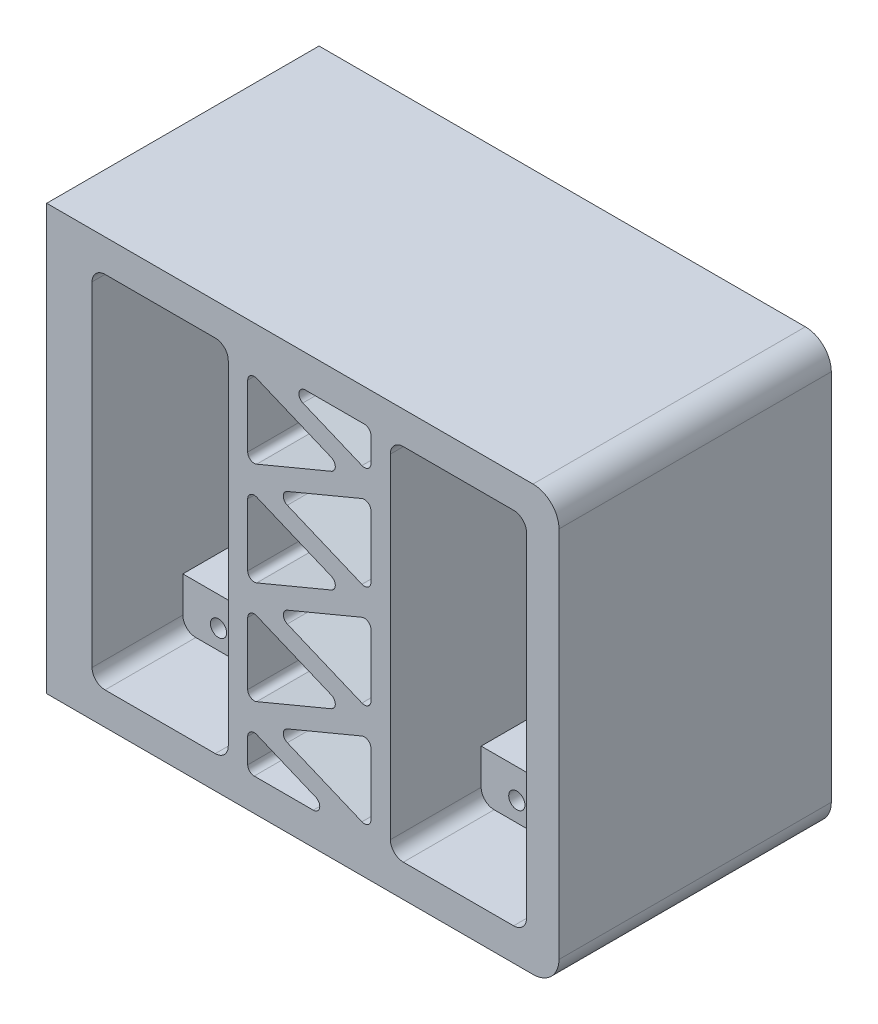
SolidWorks part; units mm, degrees
ref_plane "Front Plane" through (0, 0, 0) normal (0, 0, 1) x (1, 0, 0)
ref_plane "Top Plane" through (0, 0, 0) normal (0, 1, 0) x (1, 0, 0)
ref_plane "Right Plane" through (0, 0, 0) normal (1, 0, 0) x (0, 0, -1)
sketch "Sketch1" plane through (0, 0, 0) normal (0, 0, 1) x (1, 0, 0)
  line L0 (5, 60.5) -> (26, 60.5)
  line L1 (0, 0) -> (77, 0)
  line L2 (0, 0) -> (0, 65.5)
  line L3 (0, 65.5) -> (77, 65.5)
  line L4 (77, 0) -> (77, 65.5)
  line L5 (51, 60.5) -> (72, 60.5)
  line L6 (51, 60.5) -> (51, 5)
  line L7 (51, 5) -> (72, 5)
  line L8 (72, 60.5) -> (72, 5)
  line L9 (5, 60.5) -> (5, 5)
  line L10 (5, 5) -> (26, 5)
  line L12 (26, 60.5) -> (26, 5)
  line L13 (5, 53) -> (26, 53)
  line L14 (51, 53) -> (72, 53)
  line L15 (5, 12.5) -> (26, 12.5)
  line L16 (51, 12.5) -> (72, 12.5)
  line L17 (10.5, 57.5) -> (20.5, 57.5) construction
  line L18 (10.5, 8) -> (20.5, 8) construction
  line L19 (15.5, 57.5) -> (15.5, 8) construction
  line L20 (5, 32.75) -> (26, 32.75) construction
  line L21 (51, 32.75) -> (72, 32.75) construction
  line L22 (61.5, 57.5) -> (61.5, 8) construction
  line L23 (56.5, 57.5) -> (66.5, 57.5) construction
  line L24 (56.5, 8) -> (66.5, 8) construction
  circle A0 centre (10.5, 57.5) radius 1.25
  circle A1 centre (20.5, 57.5) radius 1.25
  circle A2 centre (10.5, 8) radius 1.25
  circle A3 centre (20.5, 8) radius 1.25
  circle A4 centre (56.5, 57.5) radius 1.25
  circle A5 centre (66.5, 57.5) radius 1.25
  circle A6 centre (66.5, 8) radius 1.25
  circle A7 centre (56.5, 8) radius 1.25
  point P33 (15.5, 32.75)
  point P34 (15.5, 32.75)
  point P41 (61.5, 32.75)
  point P42 (61.5, 32.75)
  point P53 (61.5, 8)
  point P55 (61.5, 57.5)
  dimension "D13" = 2.5
  dimension "D1" = 21
  dimension "D2" = 5
  dimension "D3" = 55.5
  dimension "D4" = 55.5
  dimension "D5" = 21
  dimension "D6" = 5
  dimension "D7" = 5
  dimension "D8" = 25
  dimension "D9" = 5
  dimension "D10" = 7.5
  dimension "D11" = 7.5
  dimension "D12" = 10
  dimension "D15" = 49.5
extrude "Boss-Extrude2" add sketch "Sketch1" against normal blind 28 contours L1 L4 L3 L2 L5 L8 L7 L6 L0 L12 L10 L9 | L9 L13 L12 L0 | L15 L9 L10 L12 | L16 L6 L7 L8 | L6 L14 L8 L5 | A0 | A1 | A4 | A5 | A6 | A7 | A3 | A2 region at (15.5, 56.7001, 0) region at (15.5, 8.7999, 0) region at (38.5, 32.75, 0) region at (61.5, 56.7001, 0) region at (61.5, 8.7999, 0) region at (10.5, 57.5, 0) region at (20.5, 57.5, 0) region at (56.5, 57.5, 0) region at (66.5, 57.5, 0) region at (66.5, 8, 0) region at (56.5, 8, 0)
extrude "Boss-Extrude4" add sketch "Sketch1<4>" along normal blind 14 contours L1 L4 L3 L2 L5 L8 L7 L6 L0 L12 L10 L9 region at (38.5, 32.75, 0)
sketch "Sketch1<4>" plane through (0, 0, 0) normal (0, 0, 1) x (1, 0, 0) same geometry as "Sketch1"
extrude "Cut-Extrude1" cut sketch "Sketch1<5>" against normal blind 12 contours A0 | A2 | A3 | A7 | A6 | A4 | A1 | A5 region at (10.5, 57.5, 0) region at (10.5, 8, 0) region at (20.5, 8, 0) region at (56.5, 57.5, 0) region at (66.5, 8, 0) region at (56.5, 8, 0)
sketch "Sketch1<5>" plane through (0, 0, 0) normal (0, 0, 1) x (1, 0, 0) same geometry as "Sketch1"
sketch "Sketch5" plane through (0, 0, 14) normal (0, 0, 1) x (1, 0, 0)
  line L0 (28.4223, 59.1157) -> (44.105, 52.5714)
  line L1 (26, 5) -> (51, 5)
  line L2 (26, 5) -> (26, 60.5)
  line L3 (26, 60.5) -> (51, 60.5)
  line L4 (51, 5) -> (51, 60.5)
  line L5 (26, 60.5) -> (26, 5) construction
  line L6 (51, 60.5) -> (51, 5) construction
  line L7 (5, 60.5) -> (26, 60.5) construction
  line L8 (5, 5) -> (26, 5) construction
  line L9 (29, 60.5) -> (48, 60.5)
  line L10 (48, 5) -> (48, 60.5)
  line L11 (29, 5) -> (48, 5)
  line L12 (29, 5) -> (29, 60.5)
  line L13 (29, 60.5) -> (48, 52.5714)
  line L14 (48, 52.5714) -> (29, 44.6429)
  line L15 (29, 44.6429) -> (48, 36.7143)
  line L16 (48, 36.7143) -> (29, 28.7857)
  line L17 (29, 28.7857) -> (48, 20.8571)
  line L18 (48, 20.8571) -> (29, 12.9286)
  line L19 (29, 12.9286) -> (48, 5)
  line L20 (44.105, 52.5714) -> (25.105, 44.6429)
  line L21 (25.105, 44.6429) -> (44.105, 36.7143)
  line L22 (44.105, 36.7143) -> (25.105, 28.7857)
  line L23 (25.105, 28.7857) -> (44.105, 20.8571)
  line L24 (44.105, 20.8571) -> (25.105, 12.9286)
  line L25 (25.105, 12.9286) -> (47.4223, 3.6157)
  line L26 (29.5777, 61.8843) -> (51.895, 52.5714)
  line L27 (51.895, 52.5714) -> (32.895, 44.6429)
  line L28 (32.895, 44.6429) -> (51.895, 36.7143)
  line L29 (51.895, 36.7143) -> (32.895, 28.7857)
  line L30 (32.895, 28.7857) -> (51.895, 20.8571)
  line L31 (51.895, 20.8571) -> (32.895, 12.9286)
  line L32 (32.895, 12.9286) -> (48.5777, 6.3843)
  dimension "D2" = 1.5
  dimension "D1" = 3
  dimension "D4" = 3
  dimension "D3" = 1.5
extrude "Cut-Extrude2" cut sketch "Sketch5" against normal through all contours L20 L0 L12 | L9 L26 L10 | L27 L28 L10 | L22 L21 L12 | L29 L30 L10 | L24 L23 L12 | L31 L32 L10 | L25 L12 L11 region at (34.035, 52.5714, 14) region at (42.965, 58.3989, 14) region at (34.035, 36.7143, 14) region at (42.965, 44.6429, 14) region at (42.965, 28.7857, 14) region at (34.035, 20.8571, 14) region at (42.965, 12.9286, 14) region at (34.035, 7.1011, 14)
fillet "Fillet4" radius 1 24 edges at (44.105, 5, -7) (29, 11.3032, -7) (29, 5, -7) (48, 6.6254, -7) (48, 19.2318, -7) (32.895, 12.9286, -7) (29, 14.5539, -7) (29, 27.1604, -7) (44.105, 20.8571, -7) (48, 22.4825, -7) (48, 35.0889, -7) (32.895, 28.7857, -7) (44.105, 36.7143, -7) (29, 30.4111, -7) (29, 43.0175, -7) (48, 38.3396, -7) (32.895, 44.6429, -7) (48, 50.9461, -7) (29, 46.2682, -7) (44.105, 52.5714, -7) (29, 58.8746, -7) (48, 54.1968, -7) (48, 60.5, -7) (32.895, 60.5, -7)
sketch "Sketch8" plane through (0, 12.5, 0) normal (0, 1, 0) x (1, 0, 0)
  line L0 (26, 28) -> (26, 0) construction
  line L1 (5, 28) -> (26, 28)
  line L2 (5, 28) -> (5, 8)
  line L3 (5, 8) -> (26, 8)
  line L4 (26, 28) -> (26, 8)
  line L5 (51, 0) -> (72, 0) construction
  line L6 (51, 28) -> (67, 28)
  line L7 (51, 28) -> (51, 8)
  line L8 (51, 8) -> (67, 8)
  line L9 (67, 28) -> (67, 8)
  dimension "D1" = 8
extrude "Cut-Extrude8" cut sketch "Sketch8" against normal blind 10
ref_plane "Midplane" through (0, 32.75, 0) normal (0, 1, 0) x (1, 0, 0)
ref_plane "Plane2" through (61.5, 0, 0) normal (1, 0, 0) x (0, 0, -1)
ref_plane "Plane3" through (15.5, 0, 0) normal (1, 0, 0) x (0, 0, -1)
sketch "Sketch10" plane through (61.5, 0, 0) normal (1, 0, 0) x (0, 0, -1)
  line L0 (28, 2.5) -> (8, 2.5) construction
  line L1 (8, 2.5) -> (8, 12.5) construction
  line L2 (28, 2.5) -> (8, 2.5)
  line L3 (8, 2.5) -> (8, 12.5)
  line L4 (8, 12.5) -> (18, 2.5)
  dimension "D1" = 45
extrude "Boss-Extrude5" add sketch "Sketch10" along normal blind 1.5 and the other way blind 1.5 contours L4 L3 L2 region at (61.5, 5.8333, -11.3333)
sketch "Sketch11" plane through (15.5, 0, 0) normal (1, 0, 0) x (0, 0, -1)
  line L0 (28, 2.5) -> (8, 2.5) construction
  line L1 (8, 2.5) -> (8, 12.5) construction
  line L2 (28, 2.5) -> (8, 2.5)
  line L3 (8, 2.5) -> (8, 12.5)
  line L4 (8, 12.5) -> (18, 2.5)
  dimension "D1" = 45
extrude "Boss-Extrude6" add sketch "Sketch11" along normal blind 1.5 and the other way blind 1.5 contours L4 L3 L2 region at (15.5, 5.8333, -11.3333)
mirror "Mirror2" about plane through (0, 32.75, 0) normal (0, 1, 0) of "Boss-Extrude6", "Boss-Extrude5", "Cut-Extrude8"
sketch "Sketch13" plane through (0, 0, 0) normal (-1, 0, 0) x (0, 0, 1)
  line L4 (-28, 0) -> (14, 0)
  line L5 (14, 0) -> (14, 65.5)
  line L6 (14, 65.5) -> (-28, 65.5)
  line L7 (-28, 65.5) -> (-28, 0)
  line L8 (-28, 0) -> (14, 0)
  line L9 (14, 0) -> (14, 65.5)
  line L10 (14, 65.5) -> (-28, 65.5)
  line L11 (-28, 65.5) -> (-28, 0)
  dimension "D1" = 0
extrude "Boss-Extrude7" add sketch "Sketch13" along normal blind 2
fillet "Fillet3" radius 2 16 edges at (51, 60.5, 7) (72, 5, 7) (72, 60.5, 7) (51, 5, 7) (5, 5, 7) (26, 5, 7) (26, 60.5, 7) (5, 60.5, 7) (67, 63, -18) (67, 2.5, -18) (51, 2.5, -18) (51, 63, -18) (26, 63, -18) (26, 2.5, -18) (5, 63, -18) (5, 2.5, -18)
sketch "Sketch14" plane through (-2, 0, 0) normal (-1, 0, 0) x (0, 0, 1)
  line L8 (-24, 61.5) -> (-24, 4)
  line L9 (-24, 4) -> (10, 4)
  line L10 (10, 4) -> (10, 61.5)
  line L11 (10, 61.5) -> (-24, 61.5)
  line L12 (-24, 61.5) -> (-24, 4) construction
  line L13 (-24, 4) -> (10, 4) construction
  line L14 (10, 4) -> (10, 61.5) construction
  line L15 (10, 61.5) -> (-24, 61.5) construction
  circle A0 centre (-24, 61.5) radius 1.25
  circle A1 centre (10, 61.5) radius 1.25
  circle A2 centre (10, 4) radius 1.25
  circle A3 centre (-24, 4) radius 1.25
  dimension "D2" = 2.5
  dimension "D1" = 4
extrude "Cut-Extrude9" cut sketch "Sketch14" against normal blind 7
fillet "Fillet7" radius 4 2 edges at (77, 65.5, -7) (77, 0, -7)
